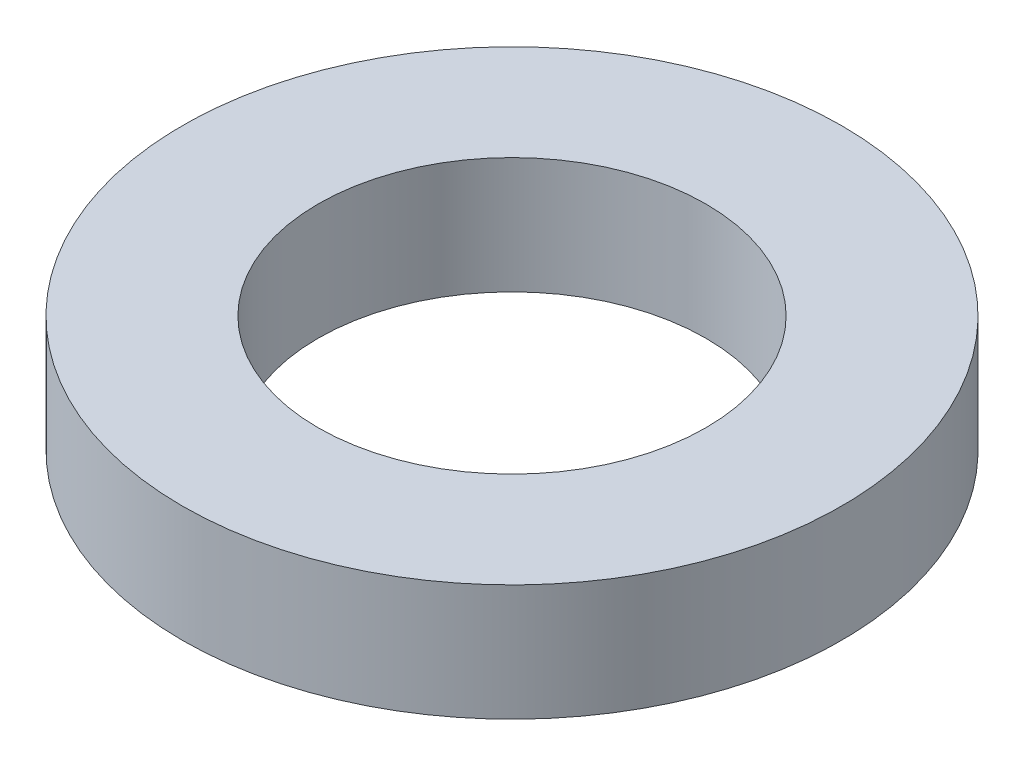
SolidWorks part; units mm, degrees
ref_plane "Front Plane" through (0, 0, 0) normal (0, 0, 1) x (1, 0, 0)
ref_plane "Top Plane" through (0, 0, 0) normal (0, 1, 0) x (1, 0, 0)
ref_plane "Right Plane" through (0, 0, 0) normal (1, 0, 0) x (0, 0, -1)
sketch "Sketch1" plane through (0, 0, 0) normal (0, 1, 0) x (1, 0, 0)
  circle A0 centre (0, 0) radius 85
  dimension "FLANGE_OD" = 170
extrude "Boss-Extrude1" add sketch "Sketch1" along normal blind 30
sketch "Sketch2" plane through (0, 0, 0) normal (0, 1, 0) x (1, 0, 0)
  circle A0 centre (0, 0) radius 50
  dimension "BORE_D" = 100
extrude "Cut-Extrude1" cut sketch "Sketch2" along normal through all
sketch "Sketch3" plane through (0, 30, 0) normal (0, 1, 0) x (1, 0, 0)
  circle A0 centre (0, 0) radius 28.9781 construction
  circle A1 centre (-28.9781, 0) radius 3.6752
  dimension "BOLT_D" = 7.3503
  dimension "BOLT_PCD" = 57.9562
extrude "Cut-Extrude2" cut sketch "Sketch3" against normal blind 23.8161 rebuild error yes
pattern_circular "CirPattern1" count 4 over 360 rebuild error yes
